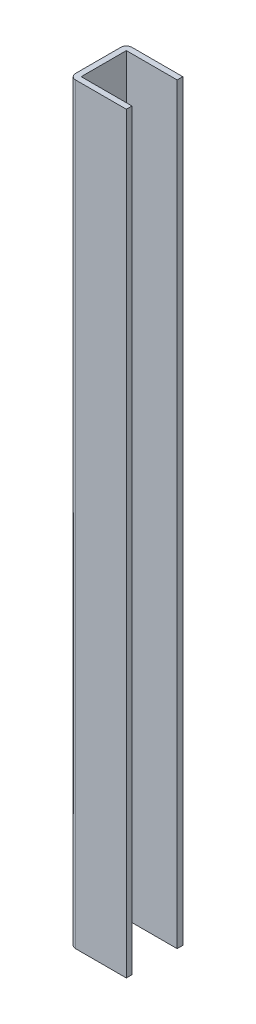
SolidWorks part; units mm, degrees
ref_plane "Спереди" through (0, 0, 0) normal (0, 0, 1) x (1, 0, 0)
ref_plane "Сверху" through (0, 0, 0) normal (0, 1, 0) x (1, 0, 0)
ref_plane "Справа" through (0, 0, 0) normal (1, 0, 0) x (0, 0, -1)
sketch "Эскиз1" plane through (0, 0, 0) normal (0, 1, 0) x (1, 0, 0)
  line L1 (-37, 15) -> (37, 15)
  line L2 (-40, 12) -> (-40, -12)
  line L3 (-37, -15) -> (37, -15)
  line L4 (40, 12) -> (40, -12)
  line L5 (-40, 15) -> (40, -15) construction
  line L6 (-40, -15) -> (40, 15) construction
  arc A0 (-37, 15) -> (-40, 12) centre (-37, 12) ccw
  arc A1 (-40, -12) -> (-37, -15) centre (-37, -12) ccw
  arc A2 (37, -15) -> (40, -12) centre (37, -12) ccw
  arc A3 (37, 15) -> (40, 12) centre (37, 12) cw
  point P0 (0, 0)
  dimension "D1" = 3
extrude "Вытянуть-Тонкостенный1" add sketch "Эскиз1" along normal blind 400 thin thin type one direction reverse wall 3
sketch "Эскиз2" plane through (0, 400, 0) normal (0, 1, 0) x (1, 0, 0)
  line L1 (-10, -23.0623) -> (41.1465, -23.0623)
  line L2 (-10, -23.0623) -> (-10, 20.9728)
  line L3 (-10, 20.9728) -> (41.1465, 20.9728)
  line L4 (41.1465, -23.0623) -> (41.1465, 20.9728)
  point P4 (-21.4718, -23.0623)
  point P5 (0, 0)
extrude "Вырез-Вытянуть1" cut sketch "Эскиз2" against normal through all
